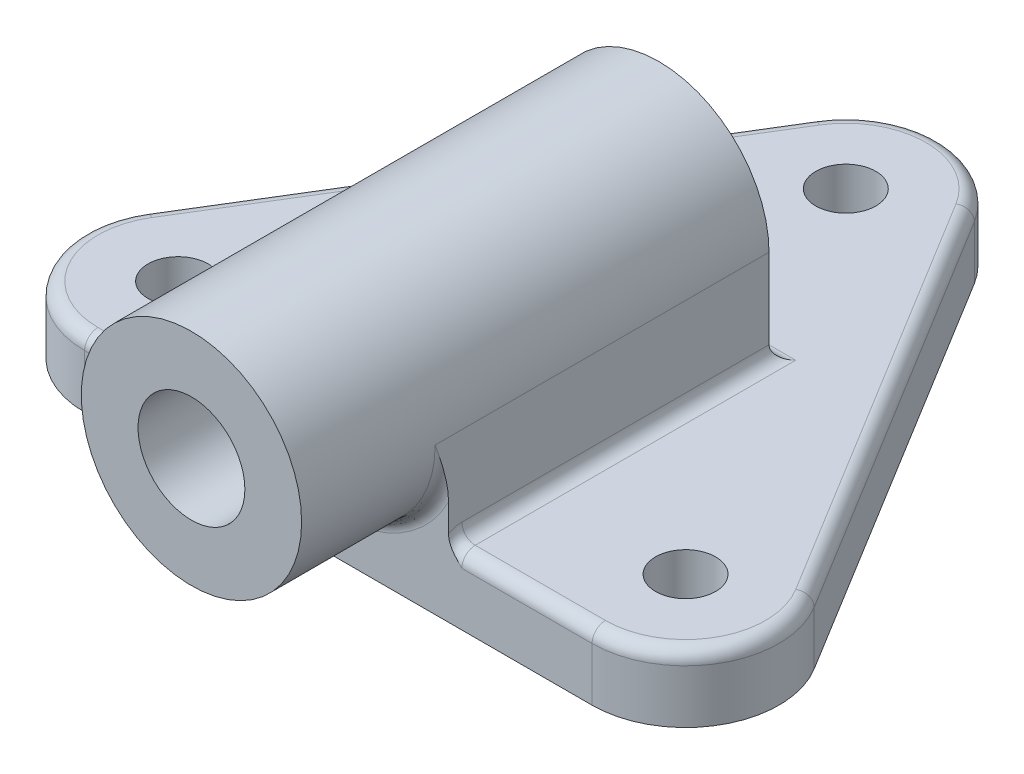
SolidWorks part; units mm, degrees
material "Brass"
ref_plane "Front Plane" through (0, 0, 0) normal (0, 0, 1) x (1, 0, 0)
ref_plane "Top Plane" through (0, 0, 0) normal (0, 1, 0) x (1, 0, 0)
ref_plane "Right Plane" through (0, 0, 0) normal (1, 0, 0) x (0, 0, -1)
sketch "Sketch1" plane through (0, 0, 0) normal (0, 1, 0) x (1, 0, 0)
  line L0 (38, 0) -> (-38, 0)
  line L1 (-49.9364, 21.3159) -> (-11.9364, 83.3159)
  line L2 (11.9364, 83.3159) -> (49.9364, 21.3159)
  arc A0 (38, 0) -> (49.9364, 21.3159) centre (38, 14) ccw
  arc A1 (-38, 0) -> (-49.9364, 21.3159) centre (-38, 14) cw
  arc A2 (-11.9364, 83.3159) -> (11.9364, 83.3159) centre (0, 76) cw
  circle A3 centre (0, 76) radius 4.5
  circle A4 centre (-38, 14) radius 4.5
  circle A5 centre (38, 14) radius 4.5
  point P4 (0, 0)
  point P7 (63.001, 0)
  point P10 (-63.001, 0)
  point P13 (0, 102.7911)
  dimension "D4" = 14
  dimension "D3" = 9
  dimension "D5" = 9
  dimension "D6" = 9
  dimension "D1" = 62
  dimension "D2" = 76
extrude "Boss-Extrude1" add sketch "Sketch1" along normal blind 10
sketch "Sketch3" plane through (0, 0, 0) normal (0, 0, 1) x (1, 0, 0)
  line L0 (-16.5, 24) -> (-16.5, 10)
  line L1 (-38, 10) -> (38, 10) construction
  line L2 (16.5, 24) -> (16.5, 10)
  circle A0 centre (0, 24) radius 16.5
  circle A1 centre (0, 24) radius 8
  line M5 (38, 10) -> (-38, 10)
  dimension "D1" = 33
  dimension "D2" = 16
  dimension "D3" = 24
  dimension "D4" = 14
extrude "Boss-Extrude2" add sketch "Sketch3" along normal blind 22 and the other way blind 48 contours A0 A1 M5 | A0 M5 | A1 region at (0, 40.0506, 0) region at (0, 8.9932, 0)
extrude "Boss-Extrude3" add sketch "Sketch3<3>" against normal blind 48 contours A0 L2 M5 | A0 L0 M5 region at (-14.3074, 13.3143, 0) region at (14.3074, 13.3143, 0)
sketch "Sketch3<3>" plane through (0, 0, 0) normal (0, 0, 1) x (1, 0, 0) same geometry as "Sketch3"
fillet "Fillet2" radius 2 7 edges at (-50.2152, 10, -7.1598) (-30.9364, 10, -52.3159) (0, 10, -90) (30.9364, 10, -52.3159) (50.2152, 10, -7.1598) (-27.25, 10, 0) (27.25, 10, 0)
fillet "Fillet3" radius 2 4 edges at (-16.5, 10, -25) (16.5, 10, -25) (-16.5, 9.4142, -0.5858) (16.5, 9.4142, -0.5858)
sketch "Sketch10" plane through (0, 0, 22) normal (0, 0, 1) x (1, 0, 0)
  circle A0 centre (0, 24) radius 8
  circle A1 centre (0, 24) radius 16.5 construction
  dimension "D2" = 16
  dimension "D3" = 8.5
  dimension "D1" = 24
extrude "Cut-Extrude1" cut sketch "Sketch10" against normal blind 54
fillet "Fillet5" radius 2 1 edges at (0, 10, -48)
fillet "Fillet6" radius 2 1 edges at (0, 7.5, 0)
